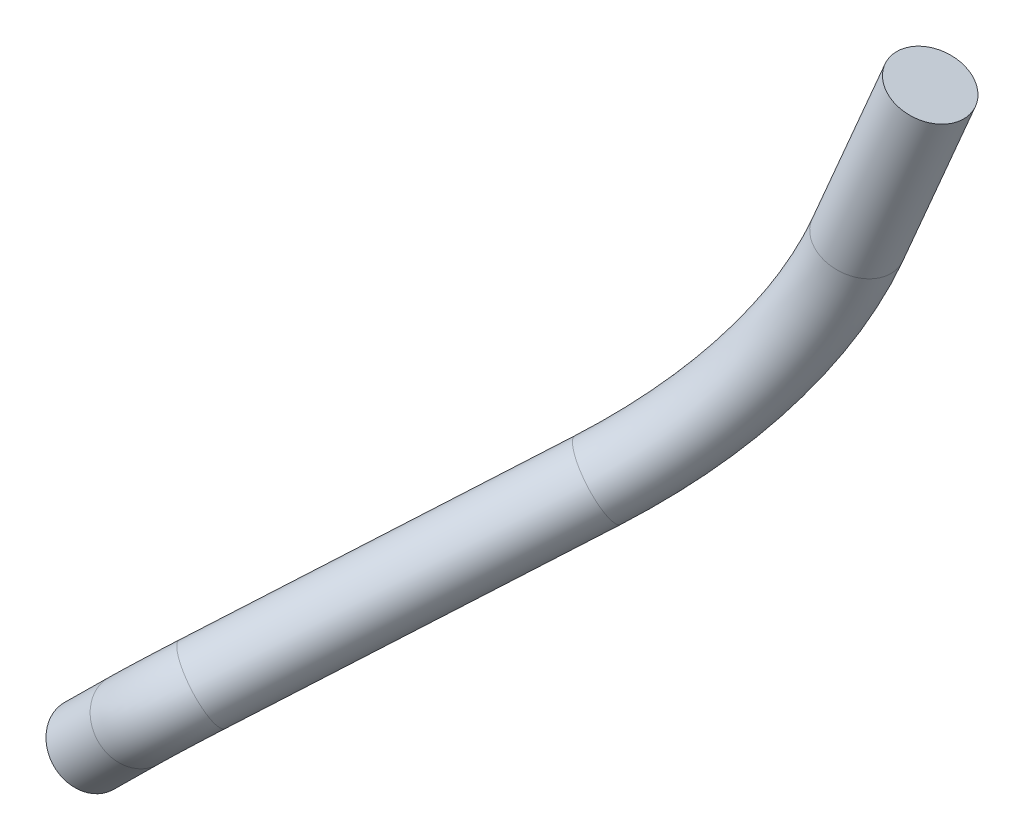
SolidWorks part; units mm, degrees
ref_plane "X-Y Datum" through (0, 0, 0) normal (0, 0, 1) x (1, 0, 0)
ref_plane "X-Z Datum" through (0, 0, 0) normal (0, 1, 0) x (1, 0, 0)
ref_plane "Y-Z Datum" through (0, 0, 0) normal (1, 0, 0) x (0, 0, -1)
sketch3d "3DSketch1"
  line L0 (245.0027, 143.553, 164.3758) -> (253.6203, 165.14, 163.3218)
  line L1 (194.7213, 86.0152, 210.3483) -> (188.8507, 80.2108, 210.3483)
  line L2 (200.7675, 91.7167, 207.26) -> (225.2152, 113.3685, 179.1128)
  line L3 (195.6578, 87.5142, 210.3483) -> (196.2341, 86.9379, 210.3483) construction
  line L4 (202.6347, 94.2501, 204.9187) -> (202.9675, 92.7853, 204.9187) construction
  arc A1 (253.6579, 165.1264, 159.3218) -> (253.6579, 165.1264, 167.3218) centre (253.6579, 165.1264, 163.3218) ccw construction
  arc A2 (253.6203, 165.14, 168.0218) -> (253.6203, 165.14, 158.6218) centre (253.6203, 165.14, 163.3218) ccw construction
  arc A3 (225.2152, 113.3685, 179.1128) -> (245.0027, 143.553, 164.3758) centre (223.0857, 154.4754, 208.8841) ccw
  arc A4 (200.7675, 91.7167, 207.26) -> (194.7213, 86.0152, 210.3483) centre (195.2886, 85.4414, 197.674) ccw
  point P0 (198.0165, 89.2733, 210.3483)
  point P1 (253.6579, 165.1264, 163.3218)
  point P5 (198.0851, 89.3411, 210.3483)
  point P9 (252.2924, 161.3666, 163.3218)
  point P17 (252.0158, 160.7224, 163.3218)
  point P18 (237.1848, 123.9692, 165.3319)
  point P19 (264.8743, 138.9837, 233.2635)
  point P21 (195.9459, 87.226, 210.3483)
  point P22 (204.1998, 76.4286, 198.4809)
  point P25 (195.9459, 87.226, 210.3483)
  point P29 (202.8011, 93.5177, 204.9187)
  point P40 (202.8011, 93.5177, 204.9187)
  dimension "D1" = 50.8
  dimension "D2" = 12.7
sweep "Sweep1" add path "3DSketch1" circular profile diameter 9.398 parameters "D3"=9.398
